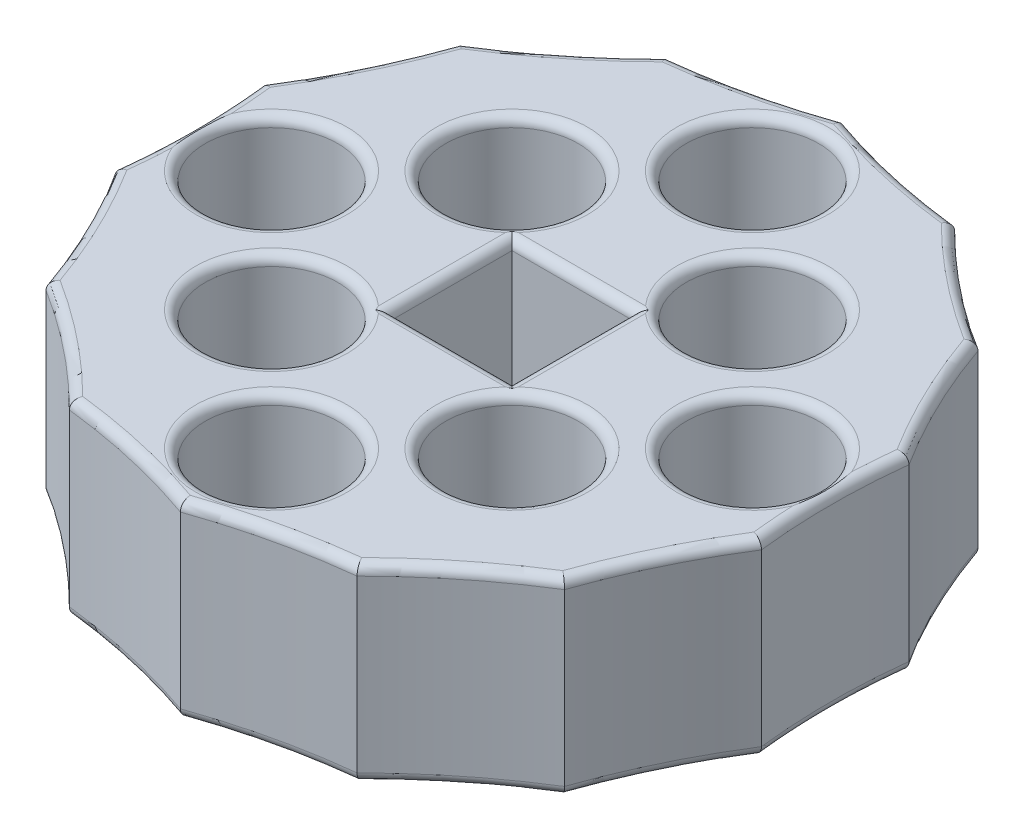
SolidWorks part; units mm, degrees
ref_plane "Front Plane" through (0, 0, 0) normal (0, 0, 1) x (1, 0, 0)
ref_plane "Top Plane" through (0, 0, 0) normal (0, 1, 0) x (1, 0, 0)
ref_plane "Right Plane" through (0, 0, 0) normal (1, 0, 0) x (0, 0, -1)
sketch "Sketch1" plane through (0, 0, 0) normal (0, 1, 0) x (1, 0, 0)
  line L1 (-3.2, 3.2) -> (3.2, 3.2)
  line L2 (-3.2, 3.2) -> (-3.2, -3.2)
  line L3 (-3.2, -3.2) -> (3.2, -3.2)
  line L4 (3.2, 3.2) -> (3.2, -3.2)
  line L5 (-3.2, 3.2) -> (3.2, -3.2) construction
  line L6 (-3.2, -3.2) -> (3.2, 3.2) construction
  arc A32 (12.7, 3.5) -> (12.7, -3.5) centre (12.7, 0) ccw
  arc A33 (12.7, -3.5) -> (12.7, 3.5) centre (12.7, 0) ccw
  arc A34 (0, 16.2) -> (0, 9.2) centre (0, 12.7) ccw
  arc A35 (0, 9.2) -> (0, 16.2) centre (0, 12.7) ccw
  arc A36 (-16.2, 0) -> (-9.2, 0) centre (-12.7, 0) ccw
  arc A37 (-9.2, 0) -> (-16.2, 0) centre (-12.7, 0) ccw
  arc A38 (-3.5, -12.7) -> (3.5, -12.7) centre (0, -12.7) ccw
  arc A39 (3.5, -12.7) -> (-3.5, -12.7) centre (0, -12.7) ccw
  arc A40 (-9.85, 6.35) -> (-2.85, 6.35) centre (-6.35, 6.35) ccw
  arc A41 (-2.85, 6.35) -> (-9.85, 6.35) centre (-6.35, 6.35) ccw
  arc A42 (-9.85, -6.35) -> (-2.85, -6.35) centre (-6.35, -6.35) ccw
  arc A43 (-2.85, -6.35) -> (-9.85, -6.35) centre (-6.35, -6.35) ccw
  arc A44 (6.35, -2.85) -> (6.35, -9.85) centre (6.35, -6.35) ccw
  arc A45 (6.35, -9.85) -> (6.35, -2.85) centre (6.35, -6.35) ccw
  arc A46 (6.35, 9.85) -> (6.35, 2.85) centre (6.35, 6.35) ccw
  arc A47 (6.35, 2.85) -> (6.35, 9.85) centre (6.35, 6.35) ccw
  arc A48 (0, 4.5) -> (0, -4.5) centre (0, 0) ccw
  arc A49 (0, -4.5) -> (0, 4.5) centre (0, 0) ccw
  arc A50 (-13.6926, -10.9189) -> (-17.0746, -3.8965) centre (-45.7962, -22.0543) ccw
  arc A51 (-7.6002, -15.7779) -> (-13.6926, -10.9189) centre (-31.694, -39.7389) ccw
  arc A52 (-0.0015, -17.5137) -> (-7.6002, -15.7779) centre (-11.3182, -49.5539) ccw
  arc A53 (7.5974, -15.7792) -> (-0.0015, -17.5137) centre (11.3095, -49.5559) ccw
  arc A54 (13.6921, -10.9205) -> (7.5974, -15.7792) centre (31.687, -39.7444) ccw
  arc A55 (17.0737, -3.8979) -> (13.6921, -10.9205) centre (45.7962, -22.0543) ccw
  arc A56 (17.0745, 3.8949) -> (17.0737, -3.8979) centre (50.83, -0.0051) ccw
  arc A57 (13.6939, 10.918) -> (17.0745, 3.8949) centre (45.7995, 22.0475) ccw
  arc A58 (7.6002, 15.778) -> (13.6939, 10.918) centre (31.695, 39.7381) ccw
  arc A59 (0.0015, 17.5135) -> (7.6002, 15.778) centre (11.3169, 49.5542) ccw
  arc A60 (-7.5975, 15.7794) -> (0.0015, 17.5135) centre (-11.3083, 49.5561) ccw
  arc A61 (-13.692, 10.9204) -> (-7.5975, 15.7794) centre (-31.688, 39.7437) ccw
  arc A62 (-17.0739, 3.8979) -> (-13.692, 10.9204) centre (-45.7957, 22.0555) ccw
  arc A63 (-17.0746, -3.8965) -> (-17.0739, 3.8979) centre (-50.83, 0.0038) ccw
  dimension "D1" = 4.5
  dimension "D4" = 3.5
  dimension "D2" = 6.4
  dimension "D3" = 6.4
extrude "Boss-Extrude1" add sketch "Sketch1" along normal blind 10 contours A63 A50 A51 A52 A53 A54 A55 A56 A57 A58 A59 A60 A61 A62 A49 A48 L3 L2 L1 L4 A47 A46 A45 A44 A43 A42 A41 A40 A39 A38 A37 A36 A35 A34 | L2 A48 | L1 A49 A48 | L4 A49 | A48 A49 L3 region at (0, 0, -3.727) region at (-3.727, 0, 0) region at (3.727, 0, 0) region at (0, 0, 3.727) region at (-14.7408, 0, 7.0982)
extrude "Cut-Extrude2" cut sketch "Sketch1<5>" along normal blind 3 contours L4 A49 | L1 A49 A48 | L2 A48 | A48 A49 L3 region at (0, 0, -3.727) region at (-3.727, 0, 0) region at (3.727, 0, 0) region at (0, 0, 3.727)
sketch "Sketch1<5>" plane through (0, 0, 0) normal (0, 1, 0) x (1, 0, 0) same geometry as "Sketch1"
fillet "Fillet3" radius 0.5 60 edges at (3.2, 0, 3.1819) (3.1819, 0, 3.2) (0, 0, 4.5) (-3.1819, 0, 3.2) (-3.2, 0, 3.1819) (-4.5, 0, 0) (-3.2, 0, -3.1819) (-3.1819, 0, -3.2) (0, 0, -4.5) (3.1819, 0, -3.2) (3.2, 0, -3.1819) (4.5, 0, 0) (12.7, 0, 3.5) (0, 0, -9.2) (-12.7, 0, 3.5) (0, 0, 16.2) (-6.35, 0, -2.85) (-6.35, 0, 9.85) (6.35, 0, 9.85) (6.35, 0, -2.85) (-15.1816, 0, 7.3104) (-10.5066, 0, 13.1732) (-3.7509, 0, 16.4272) (3.7481, 0, 16.4279) (10.505, 0, 13.1745) (15.1809, 0, 7.3119) (16.85, 0, 0.0014) (15.1822, 0, -7.3092) (10.5072, 0, -13.1727) (3.751, 0, -16.4272) (-3.7481, 0, -16.4279) (-10.5049, 0, -13.1745) (-15.1809, 0, -7.3118) (-16.85, 0, -0.0007) (12.7, 10, 3.5) (0, 10, -9.2) (-12.7, 10, 3.5) (0, 10, 16.2) (-6.35, 10, -2.85) (-6.35, 10, 9.85) (6.35, 10, 9.85) (6.35, 10, -2.85) (0, 10, -3.2) (-3.2, 10, 0) (0, 10, 3.2) (3.2, 10, 0) (-15.1809, 10, -7.3118) (-10.5049, 10, -13.1745) (-3.7481, 10, -16.4279) (3.751, 10, -16.4272) (10.5072, 10, -13.1727) (15.1822, 10, -7.3092) (16.85, 10, 0.0014) (15.1809, 10, 7.3119) (10.505, 10, 13.1745) (3.7481, 10, 16.4279) (-3.7509, 10, 16.4272) (-10.5066, 10, 13.1732) (-15.1816, 10, 7.3104) (-16.85, 10, -0.0007)
